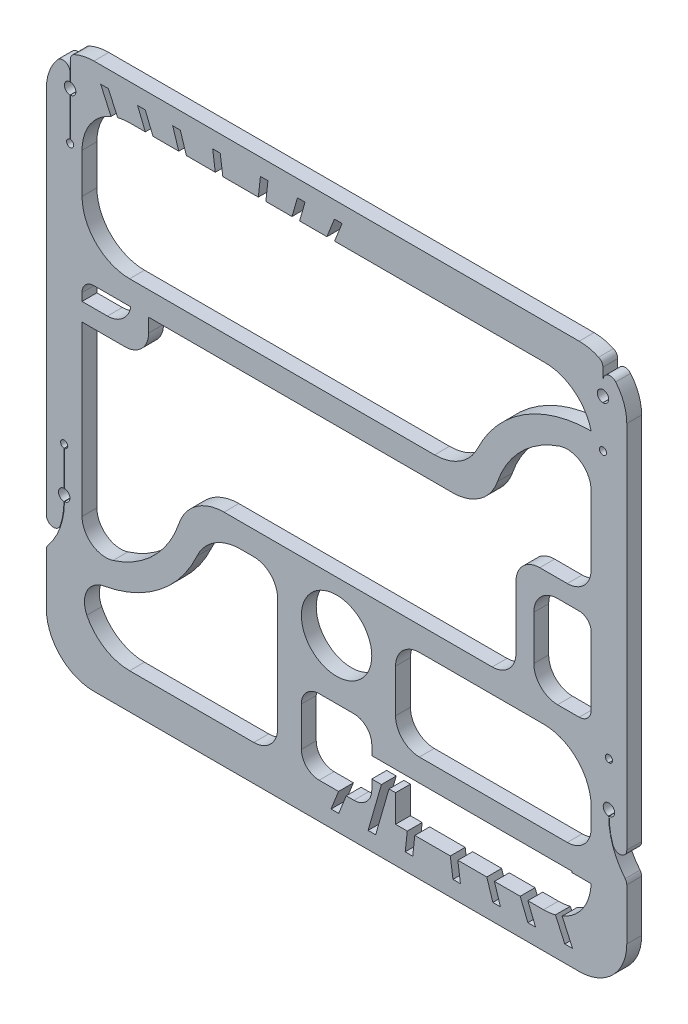
SolidWorks part; units mm, degrees
ref_plane "Front Plane" through (0, 0, 0) normal (0, 0, 1) x (1, 0, 0)
ref_plane "Top Plane" through (0, 0, 0) normal (0, 1, 0) x (1, 0, 0)
ref_plane "Right Plane" through (0, 0, 0) normal (1, 0, 0) x (0, 0, -1)
sketch "Sketch1" plane through (0, 0, 0) normal (0, 0, 1) x (1, 0, 0)
  line L0 (44.642, 21.8842) -> (44.642, 18.0742) construction
  line L1 (-10.1934, 21.8842) -> (51.7832, 21.8842)
  line L2 (-10.1934, 21.8842) -> (-10.1934, -36.406)
  line L3 (-10.1934, -36.406) -> (51.7832, -36.406)
  line L4 (51.7832, 21.8842) -> (51.7832, -36.406)
  line L5 (47.9732, -32.596) -> (-6.3834, -32.596)
  line L6 (47.9732, -32.596) -> (47.9732, 18.0742)
  line L7 (47.9732, 18.0742) -> (-6.3834, 18.0742)
  line L8 (-6.3834, -32.596) -> (-6.3834, 18.0742)
  line L9 (44.642, 19.9792) -> (-35.1587, 19.9792) construction
  line L10 (-6.3834, -31.0517) -> (-10.1934, -31.0517) construction
  line L11 (-8.2884, -31.0517) -> (-8.2884, 6.9585) construction
  line L12 (20.6521, 19.9792) -> (21.1982, 19.9792) construction
  line L14 (3.0779, -32.596) -> (3.0779, -36.406) construction
  line L15 (3.0779, -34.501) -> (37.3423, -34.501) construction
  line L16 (47.9732, -11.8991) -> (47.9732, 12.9942) construction
  line L17 (51.7832, 15.2205) -> (47.9732, 15.2205) construction
  line L18 (49.8782, 15.2205) -> (49.8782, -0.9437) construction
  line L20 (20.9378, -34.501) -> (20.3916, -34.501) construction
  line L21 (-6.3834, 8.0412) -> (-6.3834, -11.8991) construction
  dimension "D1" = 3.81
  dimension "D2" = 3.81
extrude "Boss-Extrude1" add sketch "Sketch1" along normal blind 1.5875
sketch "Sketch2" plane through (0, 0, 0) normal (0, 0, -1) x (-1, 0, 0)
  line L0 (-47.9732, -32.596) -> (-47.9732, 18.0742) construction
  line L1 (-34.8696, 3.653) -> (6.3834, 3.653)
  line L2 (-47.9732, 3.653) -> (-47.9732, 0.8076)
  line L3 (-37.4096, 1.113) -> (6.3834, 1.113)
  line L4 (6.3834, 3.653) -> (6.3834, 1.113)
  line L5 (6.3834, 18.0742) -> (6.3834, -32.596) construction
  line L6 (-33.4496, 1.113) -> (-36.4496, 1.113) construction
  line L7 (1.2504, -12.887) -> (-36.4496, -12.887) construction
  line L8 (-47.9732, -15.427) -> (-6.8239, -15.427)
  line L9 (-47.9732, -15.427) -> (-47.9732, -12.887)
  line L10 (-47.9732, -12.887) -> (-4.5259, -12.887)
  line L11 (1.357, -21.2563) -> (14.2432, -21.2563) construction
  line L12 (6.3834, -23.7963) -> (6.3834, -26.3363)
  line L13 (-47.9732, 14.2166) -> (-47.9732, 11.6766)
  arc A0 (-47.9732, 11.6766) -> (-37.4096, 1.113) centre (-47.9732, 1.113) cw
  arc A1 (-47.9732, 14.2166) -> (-34.8696, 3.653) centre (-47.9732, 0.8076) cw
  arc A2 (6.3834, -23.7963) -> (-4.5259, -12.887) centre (6.3834, -12.887) cw
  arc A3 (-6.8239, -15.427) -> (6.3834, -26.3363) centre (6.3834, -12.887) ccw
  circle A5 centre (1.357, -18.2591) radius 2.9972 construction
  line M5 (-47.9732, -32.596) -> (-47.9732, 18.0742)
  line M7 (6.3834, 18.0742) -> (6.3834, -32.596)
  dimension "D5" = 2.54
  dimension "D1" = 2.54
  dimension "D2" = 2.54
  dimension "D3" = 2.54
  dimension "D4" = 2.54
  dimension "D6" = 2.54
  dimension "D7" = 2.54
extrude "Boss-Extrude2" add sketch "Sketch2" against normal up to surface (1.5875 mm away) contours A1 A0 L3 L1 M5 M7 | L10 L8 M5 M7 region at (14.2431, 3.0939, 0) region at (-5.8234, -25.0663, 0) up to face at (20.7949, -7.2609, 1.5875)
sketch "Sketch3" plane through (0, 0, 0) normal (0, 0, -1) x (-1, 0, 0)
  line L0 (-47.9732, -1.1649) -> (-39.9496, -1.1649)
  line L1 (-47.9732, -12.887) -> (-47.9732, 11.6766) construction
  line L2 (-39.9496, -4.387) -> (-39.9496, -11.387) construction
  line L3 (-39.9496, -1.1649) -> (-39.9496, -12.887)
  line L4 (-47.9732, -12.887) -> (-4.5259, -12.887) construction
  line L5 (-39.9496, -12.887) -> (-41.8546, -12.887)
  line L6 (-41.8546, -12.887) -> (-41.8546, -3.0699)
  line L7 (-41.8546, -3.0699) -> (-47.9732, -3.0699)
  line L8 (-47.9732, -3.0699) -> (-47.9732, -1.1649)
  line L9 (-42.9468, 0.7401) -> (-53.4831, 0.7401) construction
  line L10 (-0.7296, 1.113) -> (-0.7296, -2.887)
  line L11 (-37.4096, 1.113) -> (6.3834, 1.113) construction
  line L12 (-1.9996, -2.887) -> (1.2504, -2.887) construction
  line L13 (-0.7296, -2.887) -> (6.3834, -2.887)
  line L14 (6.3834, 1.113) -> (6.3834, -23.7963) construction
  line L15 (6.3834, -2.887) -> (6.3834, -0.982)
  line L16 (6.3834, -0.982) -> (1.1754, -0.982)
  line L17 (1.1754, -0.982) -> (1.1754, 1.113)
  line L18 (1.1754, 1.113) -> (-0.7296, 1.113)
  circle A0 centre (-42.9468, 3.7373) radius 2.9972 construction
  dimension "D1" = 1.905
  dimension "D2" = 1.905
  dimension "D3" = 1.905
  dimension "D4" = 1.905
  dimension "D5" = 1.27
  dimension "D6" = 1.905
extrude "Boss-Extrude3" add sketch "Sketch3" against normal up to surface (1.5875 mm away) up to face at (20.8645, -5.9566, 1.5875)
fillet "Fillet1" radius 5.08 4 edges at (51.7832, -36.406, 0.7937) (-10.1934, -36.406, 0.7937) (-10.1934, 21.8842, 0.7937) (51.7832, 21.8842, 0.7937)
fillet "Fillet2" radius 5.08 10 edges at (6.8239, -15.427, 0.7937) (47.9732, -15.427, 0.7937) (47.9732, -32.596, 0.7937) (-6.3834, -32.596, 0.7937) (34.8696, 3.653, 0.7938) (-6.3834, 3.653, 0.7937) (47.9732, 18.0742, 0.7937) (-6.3834, 18.0742, 0.7937) (4.5259, -12.887, 0.7937) (37.4096, 1.113, 0.7938)
fillet "Fillet3" radius 2.54 10 edges at (41.8546, -3.0699, 0.7938) (39.9496, -12.887, 0.7938) (41.8546, -12.887, 0.7938) (39.9496, -1.1649, 0.7938) (47.9732, -1.1649, 0.7938) (-1.1754, -0.982, 0.7938) (0.7296, -2.887, 0.7938) (47.9732, 11.6766, 0.7937) (-6.3834, -26.3363, 0.7937) (-6.3834, -23.7963, 0.7937)
fillet "Fillet4" radius 1.27 3 edges at (47.9732, -12.887, 0.7937) (47.9732, -3.0699, 0.7938) (-6.3834, 1.113, 0.7938)
sketch "Sketch5" plane through (0, 0, 0) normal (0, 0, -1) x (-1, 0, 0)
  line L0 (-42.8932, -15.427) -> (-10.5066, -15.427) construction
  line L1 (-27.0941, -15.427) -> (-14.4957, -15.427)
  line L2 (-27.0941, -15.427) -> (-27.0941, -32.596)
  line L3 (-27.0941, -32.596) -> (-14.4957, -32.596)
  line L4 (-14.4957, -15.427) -> (-14.4957, -32.596)
  line L5 (1.3034, -32.596) -> (-42.8932, -32.596) construction
  line L6 (-24.5541, -18.2972) -> (-27.0941, -18.2972) construction
  line L9 (-17.0357, -18.2972) -> (-14.4957, -18.2972) construction
  circle A1 centre (-20.7949, -18.2972) radius 3.7592 construction
  dimension "D1" = 2.54
extrude "Boss-Extrude4" add sketch "Sketch5" against normal up to surface (1.5875 mm away) up to face at (-4.5227, -0.0173, 1.5875)
sketch "Sketch6" plane through (0, 0, 0) normal (0, 0, -1) x (-1, 0, 0)
  circle A0 centre (-20.7949, -18.2972) radius 3.7592 construction
  circle A1 centre (-20.7949, -18.2972) radius 3.7592
extrude "Cut-Extrude2" cut sketch "Sketch6" against normal up to surface (1.5875 mm away) up to face at (4.768, -24.4396, 1.5875)
sketch "Sketch7" plane through (0, 0, 0) normal (0, 0, -1) x (-1, 0, 0)
  line L0 (-27.0941, -15.427) -> (-27.0941, -32.596) construction
  line L1 (-24.5541, -24.5964) -> (-17.0357, -24.5964)
  line L2 (-24.5541, -24.5964) -> (-24.5541, -32.596)
  line L3 (-24.5541, -32.596) -> (-17.0357, -32.596)
  line L4 (-17.0357, -24.5964) -> (-17.0357, -32.596)
  line L5 (-14.4957, -32.596) -> (-14.4957, -15.427) construction
  line L6 (1.3034, -32.596) -> (-14.4957, -32.596) construction
  line L7 (-20.7949, -22.0564) -> (-6.5424, -22.0564) construction
  line L8 (-20.7949, -15.2492) -> (-20.7949, -14.538) construction
  circle A0 centre (-20.7949, -18.2972) radius 3.7592 construction
  dimension "D1" = 2.54
  dimension "D2" = 2.54
  dimension "D3" = 2.54
extrude "Cut-Extrude3" cut sketch "Sketch7" against normal up to surface (1.5875 mm away) up to face at (24.5541, -18.2972, 1.5875)
fillet "Fillet5" radius 1.905 4 edges at (24.5541, -32.596, 0.7937) (17.0357, -32.596, 0.7938) (17.0357, -24.5964, 0.7938) (24.5541, -24.5964, 0.7938)
sketch "Sketch8" plane through (0, 0, 0) normal (0, 0, -1) x (-1, 0, 0)
  line L0 (-47.9732, -27.516) -> (-47.9732, -20.507) construction
  line L1 (-47.9732, -25.103) -> (-27.0941, -25.103)
  line L2 (-47.9732, -25.103) -> (-47.9732, -27.643)
  line L3 (-47.9732, -27.643) -> (-27.0941, -27.643)
  line L4 (-27.0941, -25.103) -> (-27.0941, -27.643)
  line L5 (-27.0941, -15.427) -> (-27.0941, -32.596) construction
  line L6 (-45.7916, -27.643) -> (-20.3916, -27.643) construction
  dimension "D1" = 2.54
extrude "Boss-Extrude5" add sketch "Sketch8" against normal up to surface (1.5875 mm away) up to face at (20.7949, -28.5962, 1.5875)
fillet "Fillet6" radius 2.54 5 edges at (27.0941, -15.427, 0.7937) (14.4957, -15.427, 0.7937) (14.4957, -32.596, 0.7937) (27.0941, -25.103, 0.7937) (47.9732, -25.103, 0.7937)
sketch "Sketch4" plane through (0, 0, 0) normal (0, 0, -1) x (-1, 0, 0)
  line L0 (3.2504, -2.887) -> (4.7504, -4.387) construction
  line L1 (4.7504, -11.387) -> (3.2504, -12.887) construction
  line L2 (3.2504, -2.887) -> (4.7504, -4.387)
  line L3 (4.7504, -11.387) -> (3.2504, -12.887)
  line L4 (4.7504, -4.387) -> (4.7504, -11.387) construction
  line L5 (4.7504, -4.387) -> (4.7504, -11.387)
  line L6 (3.2504, -2.887) -> (3.2504, -12.887)
  line L32 (4.2018, 13.1212) -> (4.2018, 15.0262)
  line L33 (4.2018, 15.0262) -> (1.9539, 15.0262)
  line L34 (1.9539, 15.0262) -> (4.2018, 19.9792)
  line L35 (4.2018, 19.9792) -> (3.6556, 19.9792)
  line L36 (3.6556, 19.9792) -> (1.4078, 15.0262)
  line L37 (1.4078, 15.0262) -> (-1.7417, 15.0262)
  line L38 (-1.7417, 15.0262) -> (0.2648, 19.9792)
  line L39 (0.2648, 19.9792) -> (-0.2814, 19.9792)
  line L40 (-0.2814, 19.9792) -> (-2.2879, 15.0262)
  line L41 (-2.2879, 15.0262) -> (-5.0437, 15.0262)
  line L42 (-5.0437, 15.0262) -> (-3.469, 19.9792)
  line L43 (-3.469, 19.9792) -> (-4.0152, 19.9792)
  line L44 (-4.0152, 19.9792) -> (-5.5899, 15.0262)
  line L45 (-5.5899, 15.0262) -> (-8.3965, 15.0262)
  line L46 (-8.3965, 15.0262) -> (-7.7108, 19.9792)
  line L47 (-7.7108, 19.9792) -> (-8.257, 19.9792)
  line L48 (-8.257, 19.9792) -> (-8.9427, 15.0262)
  line L49 (-8.9427, 15.0262) -> (-12.2319, 15.0262)
  line L50 (-12.2319, 15.0262) -> (-12.7781, 19.9792)
  line L51 (-12.7781, 19.9792) -> (-13.3242, 19.9792)
  line L52 (-13.3242, 19.9792) -> (-12.7781, 15.0262)
  line L53 (-12.7781, 15.0262) -> (-15.2926, 15.0262)
  line L54 (-15.2926, 15.0262) -> (-16.7151, 19.9792)
  line L55 (-16.7151, 19.9792) -> (-17.2612, 19.9792)
  line L56 (-17.2612, 19.9792) -> (-15.8388, 15.0262)
  line L57 (-15.8388, 15.0262) -> (-18.6963, 15.0262)
  line L58 (-18.6963, 15.0262) -> (-20.6521, 19.9792)
  line L59 (-20.6521, 19.9792) -> (-21.1982, 19.9792)
  line L60 (-21.1982, 19.9792) -> (-19.2425, 15.0262)
  line L61 (-19.2425, 15.0262) -> (-21.1982, 15.0262)
  line L62 (-21.1982, 15.0262) -> (-21.1982, 13.1212)
  line L63 (-21.1982, 13.1212) -> (4.2018, 13.1212)
  line L64 (4.2018, 13.1212) -> (4.2018, 15.0262) construction
  line L65 (4.2018, 15.0262) -> (1.9539, 15.0262) construction
  line L66 (1.9539, 15.0262) -> (4.2018, 19.9792) construction
  line L67 (4.2018, 19.9792) -> (3.6556, 19.9792) construction
  line L68 (3.6556, 19.9792) -> (1.4078, 15.0262) construction
  line L69 (1.4078, 15.0262) -> (-1.7417, 15.0262) construction
  line L70 (-1.7417, 15.0262) -> (0.2648, 19.9792) construction
  line L71 (0.2648, 19.9792) -> (-0.2814, 19.9792) construction
  line L72 (-0.2814, 19.9792) -> (-2.2879, 15.0262) construction
  line L73 (-2.2879, 15.0262) -> (-5.0437, 15.0262) construction
  line L74 (-5.0437, 15.0262) -> (-3.469, 19.9792) construction
  line L75 (-3.469, 19.9792) -> (-4.0152, 19.9792) construction
  line L76 (-4.0152, 19.9792) -> (-5.5899, 15.0262) construction
  line L77 (-5.5899, 15.0262) -> (-8.3965, 15.0262) construction
  line L78 (-8.3965, 15.0262) -> (-7.7108, 19.9792) construction
  line L79 (-7.7108, 19.9792) -> (-8.257, 19.9792) construction
  line L80 (-8.257, 19.9792) -> (-8.9427, 15.0262) construction
  line L81 (-8.9427, 15.0262) -> (-12.2319, 15.0262) construction
  line L82 (-12.2319, 15.0262) -> (-12.7781, 19.9792) construction
  line L83 (-12.7781, 19.9792) -> (-13.3242, 19.9792) construction
  line L84 (-13.3242, 19.9792) -> (-12.7781, 15.0262) construction
  line L85 (-12.7781, 15.0262) -> (-15.2926, 15.0262) construction
  line L86 (-15.2926, 15.0262) -> (-16.7151, 19.9792) construction
  line L87 (-16.7151, 19.9792) -> (-17.2612, 19.9792) construction
  line L88 (-17.2612, 19.9792) -> (-15.8388, 15.0262) construction
  line L89 (-15.8388, 15.0262) -> (-18.6963, 15.0262) construction
  line L90 (-18.6963, 15.0262) -> (-20.6521, 19.9792) construction
  line L91 (-20.6521, 19.9792) -> (-21.1982, 19.9792) construction
  line L92 (-21.1982, 19.9792) -> (-19.2425, 15.0262) construction
  line L93 (-19.2425, 15.0262) -> (-21.1982, 15.0262) construction
  line L94 (-21.1982, 15.0262) -> (-21.1982, 13.1212) construction
  line L95 (-21.1982, 13.1212) -> (4.2018, 13.1212) construction
  line L96 (-45.7916, -27.643) -> (-45.7916, -29.548)
  line L97 (-45.7916, -29.548) -> (-43.5438, -29.548)
  line L98 (-43.5438, -29.548) -> (-45.7916, -34.501)
  line L99 (-45.7916, -34.501) -> (-45.2455, -34.501)
  line L100 (-45.2455, -34.501) -> (-42.9976, -29.548)
  line L101 (-42.9976, -29.548) -> (-39.8482, -29.548)
  line L102 (-39.8482, -29.548) -> (-41.8546, -34.501)
  line L103 (-41.8546, -34.501) -> (-41.3085, -34.501)
  line L104 (-41.3085, -34.501) -> (-39.302, -29.548)
  line L105 (-39.302, -29.548) -> (-36.5462, -29.548)
  line L106 (-36.5462, -29.548) -> (-38.1208, -34.501)
  line L107 (-38.1208, -34.501) -> (-37.5747, -34.501)
  line L108 (-37.5747, -34.501) -> (-36, -29.548)
  line L109 (-36, -29.548) -> (-33.1934, -29.548)
  line L110 (-33.1934, -29.548) -> (-33.879, -34.501)
  line L111 (-33.879, -34.501) -> (-33.3329, -34.501)
  line L112 (-33.3329, -34.501) -> (-32.6472, -29.548)
  line L113 (-32.6472, -29.548) -> (-29.358, -29.548)
  line L114 (-29.358, -29.548) -> (-28.8118, -34.501)
  line L115 (-28.8118, -34.501) -> (-28.2656, -34.501)
  line L116 (-28.2656, -34.501) -> (-28.8118, -29.548)
  line L117 (-28.8118, -29.548) -> (-26.2973, -29.548)
  line L118 (-26.2973, -29.548) -> (-24.8748, -34.501)
  line L119 (-24.8748, -34.501) -> (-24.3286, -34.501)
  line L120 (-24.3286, -34.501) -> (-25.7511, -29.548)
  line L121 (-25.7511, -29.548) -> (-22.8935, -29.548)
  line L122 (-22.8935, -29.548) -> (-20.9378, -34.501)
  line L123 (-20.9378, -34.501) -> (-20.3916, -34.501)
  line L124 (-20.3916, -34.501) -> (-22.3474, -29.548)
  line L125 (-22.3474, -29.548) -> (-20.3916, -29.548)
  line L126 (-20.3916, -29.548) -> (-20.3916, -27.643)
  line L127 (-20.3916, -27.643) -> (-45.7916, -27.643)
  line L128 (-45.7916, -27.643) -> (-45.7916, -29.548) construction
  line L129 (-45.7916, -29.548) -> (-43.5438, -29.548) construction
  line L130 (-43.5438, -29.548) -> (-45.7916, -34.501) construction
  line L131 (-45.7916, -34.501) -> (-45.2455, -34.501) construction
  line L132 (-45.2455, -34.501) -> (-42.9976, -29.548) construction
  line L133 (-42.9976, -29.548) -> (-39.8482, -29.548) construction
  line L134 (-39.8482, -29.548) -> (-41.8546, -34.501) construction
  line L135 (-41.8546, -34.501) -> (-41.3085, -34.501) construction
  line L136 (-41.3085, -34.501) -> (-39.302, -29.548) construction
  line L137 (-39.302, -29.548) -> (-36.5462, -29.548) construction
  line L138 (-36.5462, -29.548) -> (-38.1208, -34.501) construction
  line L139 (-38.1208, -34.501) -> (-37.5747, -34.501) construction
  line L140 (-37.5747, -34.501) -> (-36, -29.548) construction
  line L141 (-36, -29.548) -> (-33.1934, -29.548) construction
  line L142 (-33.1934, -29.548) -> (-33.879, -34.501) construction
  line L143 (-33.879, -34.501) -> (-33.3329, -34.501) construction
  line L144 (-33.3329, -34.501) -> (-32.6472, -29.548) construction
  line L145 (-32.6472, -29.548) -> (-29.358, -29.548) construction
  line L146 (-29.358, -29.548) -> (-28.8118, -34.501) construction
  line L147 (-28.8118, -34.501) -> (-28.2656, -34.501) construction
  line L148 (-28.2656, -34.501) -> (-28.8118, -29.548) construction
  line L149 (-28.8118, -29.548) -> (-26.2973, -29.548) construction
  line L150 (-26.2973, -29.548) -> (-24.8748, -34.501) construction
  line L151 (-24.8748, -34.501) -> (-24.3286, -34.501) construction
  line L152 (-24.3286, -34.501) -> (-25.7511, -29.548) construction
  line L153 (-25.7511, -29.548) -> (-22.8935, -29.548) construction
  line L154 (-22.8935, -29.548) -> (-20.9378, -34.501) construction
  line L155 (-20.9378, -34.501) -> (-20.3916, -34.501) construction
  line L156 (-20.3916, -34.501) -> (-22.3474, -29.548) construction
  line L157 (-22.3474, -29.548) -> (-20.3916, -29.548) construction
  line L158 (-20.3916, -29.548) -> (-20.3916, -27.643) construction
  line L159 (-20.3916, -27.643) -> (-45.7916, -27.643) construction
  line L263 (4.3288, 12.9942) -> (4.3288, 15.1532)
  line L264 (4.3288, 15.1532) -> (2.151, 15.1532)
  line L265 (2.151, 15.1532) -> (4.3989, 20.1062)
  line L266 (4.3989, 20.1062) -> (3.5738, 20.1062)
  line L267 (3.5738, 20.1062) -> (1.3259, 15.1532)
  line L268 (1.3259, 15.1532) -> (-1.5532, 15.1532)
  line L269 (-1.5532, 15.1532) -> (0.4532, 20.1062)
  line L270 (0.4532, 20.1062) -> (-0.367, 20.1062)
  line L271 (-0.367, 20.1062) -> (-2.3735, 15.1532)
  line L272 (-2.3735, 15.1532) -> (-4.8701, 15.1532)
  line L273 (-4.8701, 15.1532) -> (-3.2954, 20.1062)
  line L274 (-3.2954, 20.1062) -> (-4.1081, 20.1062)
  line L275 (-4.1081, 20.1062) -> (-5.6828, 15.1532)
  line L276 (-5.6828, 15.1532) -> (-8.2507, 15.1532)
  line L277 (-8.2507, 15.1532) -> (-7.565, 20.1062)
  line L278 (-7.565, 20.1062) -> (-8.3676, 20.1062)
  line L279 (-8.3676, 20.1062) -> (-9.0533, 15.1532)
  line L280 (-9.0533, 15.1532) -> (-12.1181, 15.1532)
  line L281 (-12.1181, 15.1532) -> (-12.6643, 20.1062)
  line L282 (-12.6643, 20.1062) -> (-13.466, 20.1062)
  line L283 (-13.466, 20.1062) -> (-12.9198, 15.1532)
  line L284 (-12.9198, 15.1532) -> (-15.1969, 15.1532)
  line L285 (-15.1969, 15.1532) -> (-16.6194, 20.1062)
  line L286 (-16.6194, 20.1062) -> (-17.4298, 20.1062)
  line L287 (-17.4298, 20.1062) -> (-16.0074, 15.1532)
  line L288 (-16.0074, 15.1532) -> (-18.6099, 15.1532)
  line L289 (-18.6099, 15.1532) -> (-20.5657, 20.1062)
  line L290 (-20.5657, 20.1062) -> (-21.3849, 20.1062)
  line L291 (-21.3849, 20.1062) -> (-19.4292, 15.1532)
  line L292 (-19.4292, 15.1532) -> (-21.3252, 15.1532)
  line L293 (-21.3252, 15.1532) -> (-21.3252, 12.9942)
  line L294 (-21.3252, 12.9942) -> (4.3288, 12.9942)
  line L295 (-45.9186, -27.516) -> (-45.9186, -29.675)
  line L296 (-45.9186, -29.675) -> (-43.7409, -29.675)
  line L297 (-43.7409, -29.675) -> (-45.9887, -34.628)
  line L298 (-45.9887, -34.628) -> (-45.1636, -34.628)
  line L299 (-45.1636, -34.628) -> (-42.9158, -29.675)
  line L300 (-42.9158, -29.675) -> (-40.0367, -29.675)
  line L301 (-40.0367, -29.675) -> (-42.0431, -34.628)
  line L302 (-42.0431, -34.628) -> (-41.2229, -34.628)
  line L303 (-41.2229, -34.628) -> (-39.2164, -29.675)
  line L304 (-39.2164, -29.675) -> (-36.7198, -29.675)
  line L305 (-36.7198, -29.675) -> (-38.2945, -34.628)
  line L306 (-38.2945, -34.628) -> (-37.4818, -34.628)
  line L307 (-37.4818, -34.628) -> (-35.9071, -29.675)
  line L308 (-35.9071, -29.675) -> (-33.3392, -29.675)
  line L309 (-33.3392, -29.675) -> (-34.0248, -34.628)
  line L310 (-34.0248, -34.628) -> (-33.2222, -34.628)
  line L311 (-33.2222, -34.628) -> (-32.5366, -29.675)
  line L312 (-32.5366, -29.675) -> (-29.4717, -29.675)
  line L313 (-29.4717, -29.675) -> (-28.9256, -34.628)
  line L314 (-28.9256, -34.628) -> (-28.1239, -34.628)
  line L315 (-28.1239, -34.628) -> (-28.67, -29.675)
  line L316 (-28.67, -29.675) -> (-26.3929, -29.675)
  line L317 (-26.3929, -29.675) -> (-24.9705, -34.628)
  line L318 (-24.9705, -34.628) -> (-24.16, -34.628)
  line L319 (-24.16, -34.628) -> (-25.5825, -29.675)
  line L320 (-25.5825, -29.675) -> (-22.9799, -29.675)
  line L321 (-22.9799, -29.675) -> (-21.0242, -34.628)
  line L322 (-21.0242, -34.628) -> (-20.205, -34.628)
  line L323 (-20.205, -34.628) -> (-22.1607, -29.675)
  line L324 (-22.1607, -29.675) -> (-20.2646, -29.675)
  line L325 (-20.2646, -29.675) -> (-20.2646, -27.516)
  line L326 (-20.2646, -27.516) -> (-45.9186, -27.516)
  dimension "D1" = 0
  dimension "D2" = 0
  dimension "D3" = 0.127
  dimension "D4" = 0.127
extrude "Cut-Extrude1" cut sketch "Sketch4" against normal up to surface (1.5875 mm away) up to face at (37.2819, -20.5167, 1.5875)
sketch "Sketch9" plane through (0, 0, 0) normal (0, 0, -1) x (-1, 0, 0)
  circle A0 centre (-49.2432, 18.0742) radius 0.6096 construction
  circle A1 centre (7.6534, 18.0742) radius 0.6096 construction
  circle A2 centre (8.2884, -19.8366) radius 0.6096 construction
  circle A3 centre (-49.8782, -19.8366) radius 0.6096 construction
  circle A4 centre (-49.2432, 18.0742) radius 0.6096
  circle A5 centre (7.6534, 18.0742) radius 0.6096
  circle A6 centre (8.2884, -19.8366) radius 0.6096
  circle A7 centre (-49.8782, -19.8366) radius 0.6096
extrude "Cut-Extrude4" cut sketch "Sketch9" against normal up to surface (1.5875 mm away) up to face at (31.4097, -31.792, 1.5875)
sketch "Sketch10" plane through (0, 0, 1.5875) normal (0, 0, 1) x (1, 0, 0)
  line L0 (-7.6407, 18.6837) -> (-7.6407, 20.7449) construction
  line L1 (-7.6407, 13.375) -> (-7.6407, 17.4647) construction
  line L2 (-7.6661, 17.4647) -> (-7.6661, 13.375) construction
  line L3 (-7.6661, 19.5715) -> (-7.6661, 18.6837) construction
  line L4 (-7.6407, 18.6837) -> (-7.6407, 20.7449)
  line L5 (-7.6407, 13.375) -> (-7.6407, 17.4647)
  line L6 (-7.6661, 17.4647) -> (-7.6661, 13.375)
  line L7 (-7.6661, 19.5715) -> (-7.6661, 18.6837)
  line L8 (49.2305, 18.6837) -> (49.2305, 20.7449) construction
  line L9 (49.2305, 13.375) -> (49.2305, 17.4647) construction
  line L10 (49.2559, 17.4647) -> (49.2559, 13.375) construction
  line L11 (49.2559, 19.5715) -> (49.2559, 18.6837) construction
  line L12 (49.2305, 18.6837) -> (49.2305, 20.7449)
  line L13 (49.2305, 13.375) -> (49.2305, 17.4647)
  line L14 (49.2559, 17.4647) -> (49.2559, 13.375)
  line L15 (49.2559, 19.5715) -> (49.2559, 18.6837)
  line L16 (49.8909, -15.5181) -> (49.8909, -19.2271) construction
  line L17 (49.8655, -15.5181) -> (49.8655, -19.2271) construction
  line L18 (49.8909, -15.5181) -> (49.8909, -19.2271)
  line L19 (49.8655, -15.5181) -> (49.8655, -19.2271)
  line L20 (-8.2757, -15.5181) -> (-8.2757, -19.2271) construction
  line L21 (-8.3011, -15.5181) -> (-8.3011, -19.2271) construction
  line L22 (-8.2757, -15.5181) -> (-8.2757, -19.2271)
  line L23 (-8.3011, -15.5181) -> (-8.3011, -19.2271)
  line L24 (51.7832, -31.326) -> (51.7832, 16.8042) construction
  line L25 (51.7832, -25.8445) -> (51.7832, -22.639)
  line L26 (-10.1934, 16.8042) -> (-10.1934, -31.326) construction
  line L27 (-10.1934, -22.639) -> (-10.1934, -25.8445)
  arc A1 (-7.1902, 21.4403) -> (-7.6407, 20.7449) centre (-6.8787, 20.7449) ccw construction
  arc A2 (-7.6661, 13.375) -> (-7.6407, 13.375) centre (-7.6534, 12.9942) ccw construction
  arc A3 (-7.6661, 19.5715) -> (-9.013, 20.0598) centre (-8.4281, 19.5715) ccw construction
  arc A4 (-5.1134, 21.8842) -> (-10.1934, 16.8042) centre (-5.1134, 16.8042) ccw construction
  arc A5 (-7.1902, 21.4403) -> (-7.6407, 20.7449) centre (-6.8787, 20.7449) ccw
  arc A6 (-7.6661, 13.375) -> (-7.6407, 13.375) centre (-7.6534, 12.9942) ccw
  arc A7 (-7.6661, 19.5715) -> (-9.013, 20.0598) centre (-8.4281, 19.5715) ccw
  arc A8 (-7.1902, 21.4403) -> (-9.013, 20.0598) centre (-5.1134, 16.8042) ccw
  circle A9 centre (-7.6534, 18.0742) radius 0.6096 construction
  arc A10 (-7.6407, 18.6837) -> (-7.6661, 18.6837) centre (-7.6534, 18.0742) ccw
  arc A11 (-7.6661, 17.4647) -> (-7.6407, 17.4647) centre (-7.6534, 18.0742) ccw
  arc A12 (49.2305, 20.7449) -> (48.7801, 21.4403) centre (48.4685, 20.7449) ccw construction
  arc A13 (49.2305, 13.375) -> (49.2559, 13.375) centre (49.2432, 12.9942) ccw construction
  arc A14 (50.6029, 20.0598) -> (49.2559, 19.5715) centre (50.0179, 19.5715) ccw construction
  arc A15 (49.2305, 20.7449) -> (48.7801, 21.4403) centre (48.4685, 20.7449) ccw
  arc A16 (49.2305, 13.375) -> (49.2559, 13.375) centre (49.2432, 12.9942) ccw
  arc A17 (50.6029, 20.0598) -> (49.2559, 19.5715) centre (50.0179, 19.5715) ccw
  arc A18 (49.8909, -15.5181) -> (49.8655, -15.5181) centre (49.8782, -15.1373) ccw construction
  arc A19 (49.9036, -20.4457) -> (50.2983, -22.8798) centre (57.6041, -20.4462) ccw construction
  arc A20 (49.8528, -20.4457) -> (51.6105, -25.3613) centre (57.6041, -20.4462) ccw construction
  arc A21 (50.2983, -22.8798) -> (51.7832, -22.639) centre (51.0212, -22.639) ccw construction
  arc A22 (51.7832, -25.8445) -> (51.6105, -25.3613) centre (51.0212, -25.8445) ccw construction
  arc A23 (49.8909, -15.5181) -> (49.8655, -15.5181) centre (49.8782, -15.1373) ccw
  arc A24 (49.9036, -20.4457) -> (50.2983, -22.8798) centre (57.6041, -20.4462) ccw
  arc A25 (49.8528, -20.4457) -> (51.6105, -25.3613) centre (57.6041, -20.4462) ccw
  arc A26 (50.2983, -22.8798) -> (51.7832, -22.639) centre (51.0212, -22.639) ccw
  arc A27 (51.7832, -25.8445) -> (51.6105, -25.3613) centre (51.0212, -25.8445) ccw
  arc A28 (-10.1934, -22.639) -> (-8.7084, -22.8798) centre (-9.4314, -22.639) ccw construction
  arc A29 (-10.0206, -25.3613) -> (-8.263, -20.4457) centre (-16.0142, -20.4462) ccw construction
  arc A30 (-8.7084, -22.8798) -> (-8.3138, -20.4457) centre (-16.0142, -20.4462) ccw construction
  arc A31 (-8.2757, -15.5181) -> (-8.3011, -15.5181) centre (-8.2884, -15.1373) ccw construction
  arc A32 (-10.1934, -22.639) -> (-8.7084, -22.8798) centre (-9.4314, -22.639) ccw
  arc A33 (-10.0206, -25.3613) -> (-8.263, -20.4457) centre (-16.0142, -20.4462) ccw
  arc A34 (-8.7084, -22.8798) -> (-8.3138, -20.4457) centre (-16.0142, -20.4462) ccw
  arc A35 (-8.2757, -15.5181) -> (-8.3011, -15.5181) centre (-8.2884, -15.1373) ccw
  arc A36 (51.7832, 16.8042) -> (46.7032, 21.8842) centre (46.7032, 16.8042) ccw construction
  arc A37 (50.6029, 20.0598) -> (48.7801, 21.4403) centre (46.7032, 16.8042) ccw
  circle A38 centre (49.2432, 18.0742) radius 0.6096 construction
  arc A39 (49.2559, 18.6837) -> (49.2305, 18.6837) centre (49.2432, 18.0742) ccw
  arc A40 (49.2305, 17.4647) -> (49.2559, 17.4647) centre (49.2432, 18.0742) ccw
  circle A41 centre (49.8782, -19.8366) radius 0.6096 construction
  arc A42 (49.8909, -19.2271) -> (49.8655, -19.2271) centre (49.8782, -19.8366) ccw
  arc A43 (49.8528, -20.4457) -> (49.9036, -20.4457) centre (49.8782, -19.8366) ccw
  circle A44 centre (-8.2884, -19.8366) radius 0.6096 construction
  arc A45 (-8.2757, -19.2271) -> (-8.3011, -19.2271) centre (-8.2884, -19.8366) ccw
  arc A46 (-8.3138, -20.4457) -> (-8.263, -20.4457) centre (-8.2884, -19.8366) ccw
  arc A47 (-10.0206, -25.3613) -> (-10.1934, -25.8445) centre (-9.4314, -25.8445) ccw construction
  arc A48 (-10.0206, -25.3613) -> (-10.1934, -25.8445) centre (-9.4314, -25.8445) ccw
extrude "Slots for carbon" cut sketch "Sketch10" against normal through all
